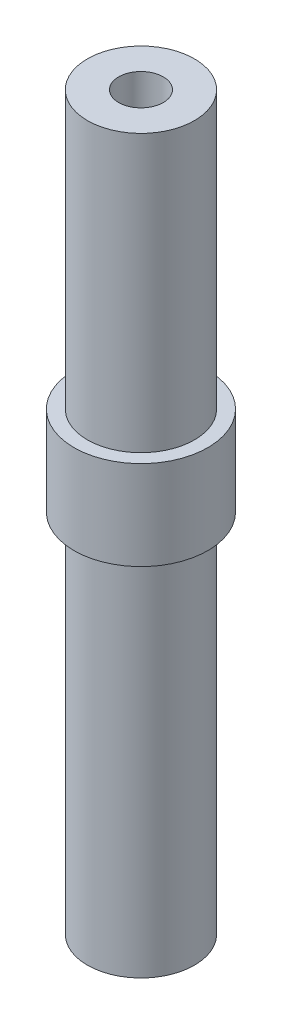
SolidWorks part; units mm, degrees
material "6061-T6 (SS)"
ref_plane "Front Plane" through (0, 0, 0) normal (0, 0, 1) x (1, 0, 0)
ref_plane "Top Plane" through (0, 0, 0) normal (0, 1, 0) x (1, 0, 0)
ref_plane "Right Plane" through (0, 0, 0) normal (1, 0, 0) x (0, 0, -1)
sketch "Sketch1" plane through (0, 0, 0) normal (0, 1, 0) x (1, 0, 0)
  circle A0 centre (0, 0) radius 3
  circle A1 centre (0, 0) radius 2 construction
  dimension "D1" = 6
  dimension "D2" = 4
extrude "Boss-Extrude1" add sketch "Sketch1" along normal blind 20.5 and the other way blind 20.5
sketch "Sketch2" plane through (0, 20.5, 0) normal (0, 1, 0) x (1, 0, 0)
  point P0 (0, 0)
hole_wizard "M3x0.5 Tapped Hole1" positions "Sketch4" profile "Sketch5" tap size "M3x0.5" standard "ANSI Metric"
sketch "Sketch4" plane through (0, 20.5, 0) normal (0, 1, 0) x (1, 0, 0)
  point P0 (0, 0)
sketch "Sketch5" plane through (0, 20.5, 0) normal (1, 0, 0) x (0, 0, 1)
  line L0 (0, 0) -> (0, 8.7511)
  line L1 (0, 8.7511) -> (1.25, 8)
  line L2 (1.25, 8) -> (1.25, 0)
  line L5 (1.25, 0) -> (0, 0)
  line L10 (0, 8.7511) -> (-1.25, 8) construction
  line L11 (0, -6.35) -> (0, 107.95) construction
  dimension "Tap Drill Dia." = 2.5
  dimension "Tap Drill Depth" = 8
  dimension "Drill Angle" = 118
cosmetic thread "Hole Thread1"
ref_plane "Plane1" through (0, 0, 0) normal (0, 1, 0) x (1, 0, 0)
sketch "Sketch6" plane through (0, 0, 0) normal (0, 1, 0) x (1, 0, 0)
  circle A0 centre (0, 0) radius 3.75
  dimension "D1" = 7.5
extrude "Boss-Extrude2" add sketch "Sketch6" along normal blind 5
mirror "Mirror1" about plane through (0, 0, 0) normal (0, 1, 0) of "M3x0.5 Tapped Hole1"
